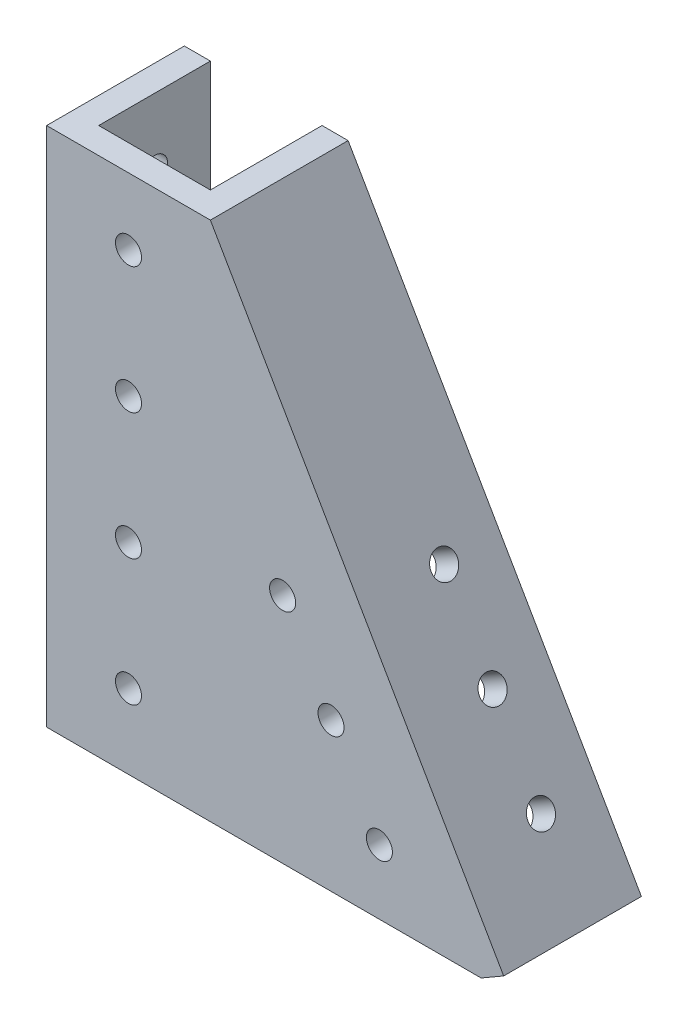
SolidWorks part; units mm, degrees
ref_plane "Front Plane" through (0, 0, 0) normal (0, 0, 1) x (1, 0, 0)
ref_plane "Top Plane" through (0, 0, 0) normal (0, 1, 0) x (1, 0, 0)
ref_plane "Right Plane" through (0, 0, 0) normal (1, 0, 0) x (0, 0, -1)
sketch "Sketch1" plane through (0, 0, 0) normal (0, 0, 1) x (1, 0, 0)
  line L0 (7.855, 37.4696) -> (48.2584, -32.5112)
  line L1 (-14.145, 37.4696) -> (7.855, 37.4696)
  line L2 (-14.145, 37.4696) -> (-14.145, -32.5112)
  line L3 (-14.145, -32.5112) -> (7.855, -32.5112)
  line L4 (7.855, 37.4696) -> (7.855, -32.5112) construction
  line L5 (48.2584, -32.5112) -> (7.855, -32.5112)
  line L6 (22.855, -32.5112) -> (7.855, -6.5304) construction
  line L7 (7.855, -6.5304) -> (44.3314, 14.5292) construction
  dimension "D1" = 22
  dimension "D2" = 30
  dimension "D3" = 22
  dimension "D4" = 30
extrude "Boss-Extrude1" add sketch "Sketch1" along normal blind 18.5
sketch "Sketch2" plane through (0, 0, 0) normal (0, 0, 1) x (1, 0, 0)
  line L0 (7.855, 37.4696) -> (-14.145, 37.4696) construction
  line L1 (-14.145, -32.5112) -> (48.2584, -32.5112) construction
  line L2 (-10.645, 37.4696) -> (4.355, 37.4696)
  line L3 (-10.645, 37.4696) -> (-10.645, -32.5112)
  line L4 (-10.645, -32.5112) -> (4.355, -32.5112)
  line L5 (4.355, 37.4696) -> (4.355, -32.5112)
  line L6 (-14.145, 37.4696) -> (-14.145, -32.5112) construction
  line L7 (44.2169, -32.5112) -> (19.8868, 9.6298)
  line L8 (19.8868, 9.6298) -> (6.8964, 2.1298)
  line L9 (6.8964, 2.1298) -> (26.8964, -32.5112)
  line L10 (26.8964, -32.5112) -> (44.2169, -32.5112)
  line L11 (48.2584, -32.5112) -> (7.855, 37.4696) construction
  dimension "D1" = 15
  dimension "D2" = 3.5
  dimension "D3" = 3.5
  dimension "D4" = 15
  dimension "D5" = 40
extrude "Cut-Extrude1" cut sketch "Sketch2" along normal offset from surface (15 mm away) 15 up to face at (6.9558, 2.4792, 0)
sketch "Sketch3" plane through (22.116, 12.7687, 0) normal (0.866, 0.5, 0) x (0, 0, -1)
  line L0 (-7.5, 30.2721) -> (-7.5, -52.2847) construction
  line L1 (-15, 30.2721) -> (0, 30.2721) construction
  line L2 (-18.5, -52.2847) -> (0, -52.2847) construction
  circle A0 centre (-7.5, -38.2847) radius 1.75
  circle A1 centre (-7.5, -25.2847) radius 1.75
  circle A2 centre (-7.5, -12.2847) radius 1.75
  dimension "D1" = 3.5
  dimension "D2" = 14
  dimension "D4" = 13
  dimension "D3" = 13
extrude "Cut-Extrude2" cut sketch "Sketch3" against normal blind 3.5
sketch "Sketch4" plane through (0, 0, 18.5) normal (0, 0, -1) x (-1, 0, 0)
  line L0 (3.145, 37.4696) -> (3.145, -32.5112) construction
  line L2 (14.145, -32.5112) -> (10.645, -32.5112) construction
  line L3 (-13.3916, 5.8798) -> (-35.5567, -32.5112) construction
  line L4 (-6.8964, 2.1298) -> (-19.8868, 9.6298) construction
  line L5 (-7.855, 37.4696) -> (14.145, 37.4696) construction
  circle A0 centre (-30.5567, -23.851) radius 1.75
  circle A1 centre (-24.0567, -12.5926) radius 1.75
  circle A2 centre (-17.5567, -1.3343) radius 1.75
  circle A3 centre (3.145, -5.5112) radius 1.75
  circle A4 centre (3.145, 11.4888) radius 1.75
  circle A5 centre (3.145, 28.4888) radius 1.75
  circle A6 centre (3.145, -22.5112) radius 1.75
  dimension "D1" = 10
  dimension "D2" = 13
  dimension "D3" = 13
  dimension "D4" = 3.5
  dimension "D5" = 4
  dimension "D6" = 10
extrude "Cut-Extrude3" cut sketch "Sketch4" along normal blind 4
sketch "Sketch5" plane through (-14.145, 0, 0) normal (-1, 0, 0) x (0, 0, 1)
  line L0 (7.5, 37.4696) -> (7.5, -32.5112) construction
  line L1 (18.5, 37.4696) -> (0, 37.4696) construction
  line L2 (18.5, -32.5112) -> (0, -32.5112) construction
  line L4 (0, 37.4696) -> (0, -32.5112) construction
  circle A0 centre (7.5, -22.5112) radius 1.75
  circle A1 centre (7.5, -5.5112) radius 1.75
  circle A2 centre (7.5, 11.4888) radius 1.75
  circle A3 centre (7.5, 28.4888) radius 1.75
  dimension "D2" = 3.5
  dimension "D3" = 10
  dimension "D1" = 7.5
  dimension "D4" = 4
extrude "Cut-Extrude4" cut sketch "Sketch5" against normal blind 4
sketch "Sketch6" plane through (0, 0, 18.5) normal (0, 0, 1) x (1, 0, 0)
  line L0 (44.2169, -32.5112) -> (47.248, -30.7612)
  line L1 (48.2584, -32.5112) -> (7.855, 37.4696) construction
  line L2 (47.248, -30.7612) -> (48.2584, -32.5112)
  line L3 (48.2584, -32.5112) -> (44.2169, -32.5112)
extrude "Cut-Extrude5" cut sketch "Sketch6" against normal blind 19
